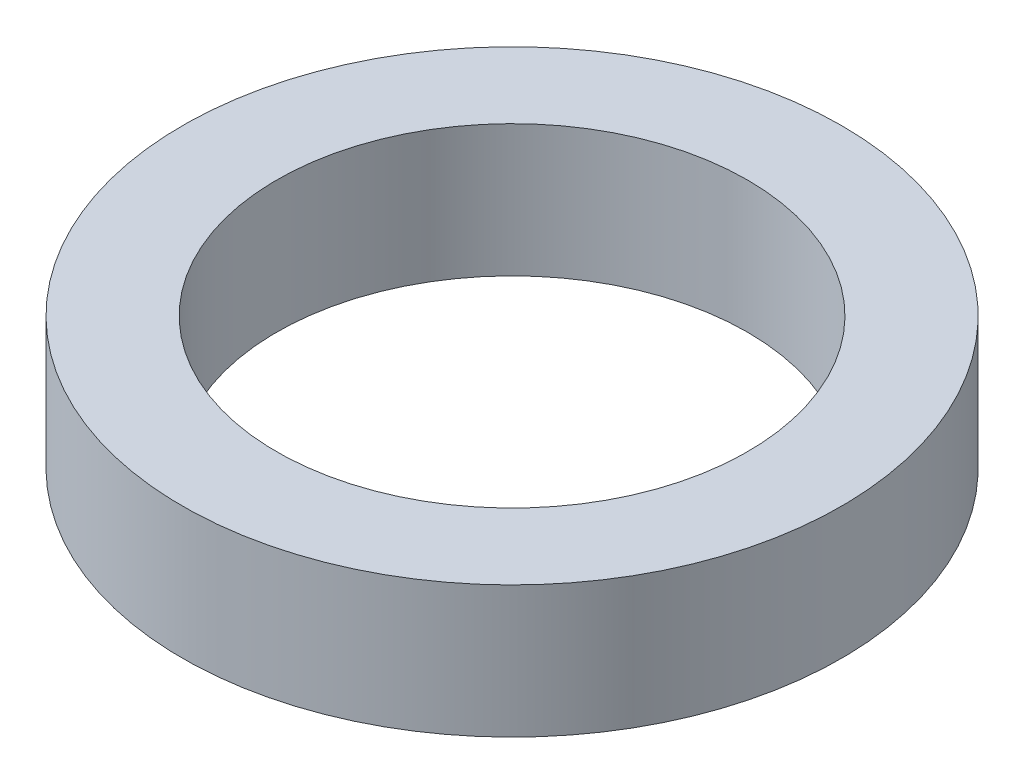
SolidWorks part; units mm, degrees
material "Plain Carbon Steel"
ref_plane "Front Plane" through (0, 0, 0) normal (0, 0, 1) x (1, 0, 0)
ref_plane "Top Plane" through (0, 0, 0) normal (0, 1, 0) x (1, 0, 0)
ref_plane "Right Plane" through (0, 0, 0) normal (1, 0, 0) x (0, 0, -1)
sketch "Sketch1" plane through (0, 0, 0) normal (1, 0, 0) x (0, 0, -1)
  line L0 (0, -36.564) -> (0, 50.9245) construction
  line L2 (-17.5, 0) -> (-12.5, 0)
  line L3 (-17.5, 0) -> (-17.5, 7)
  line L4 (-17.5, 7) -> (-12.5, 7)
  line L5 (-12.5, 0) -> (-12.5, 7)
  dimension "D1" = 12.5
  dimension "D2" = 17.5
  dimension "D3" = 7
revolve "Revolve1" add sketch "Sketch1" angle 360 about L0
